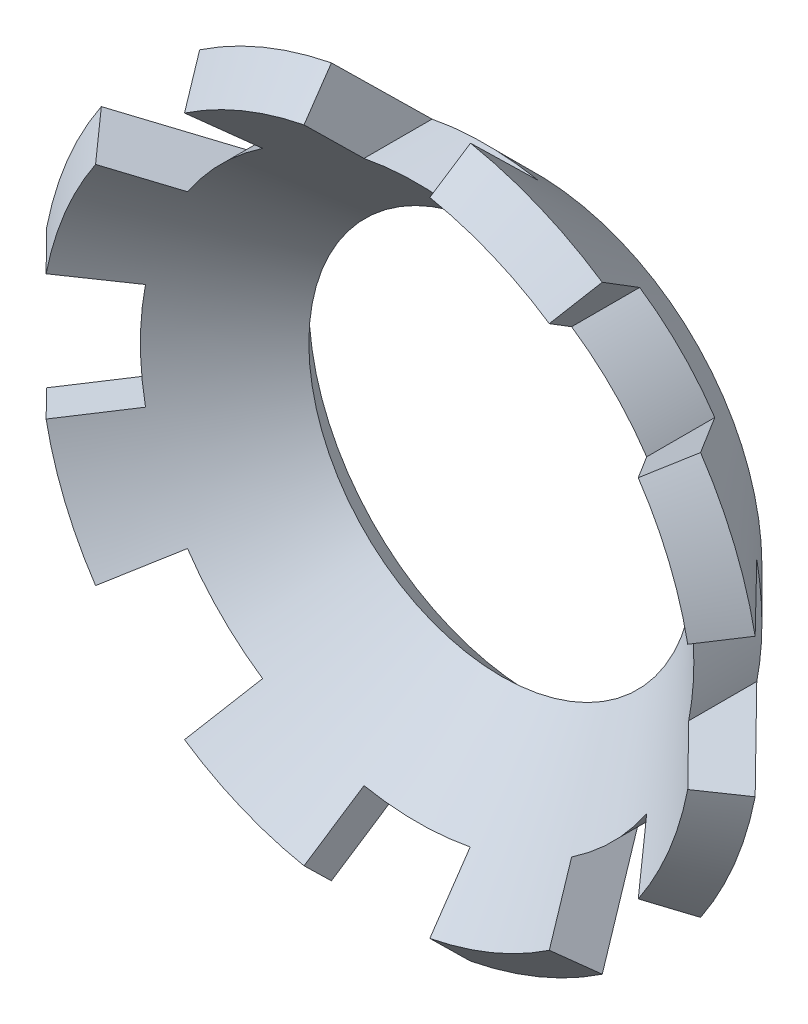
SolidWorks part; units mm, degrees
ref_plane "Front Plane" through (0, 0, 0) normal (0, 0, 1) x (1, 0, 0)
ref_plane "Top Plane" through (0, 0, 0) normal (0, 1, 0) x (1, 0, 0)
ref_plane "Right Plane" through (0, 0, 0) normal (1, 0, 0) x (0, 0, -1)
sketch "BodySke" plane through (0, 0, 0) normal (0, 1, 0) x (1, 0, 0)
  line L0 (0, -1.6) -> (0, 3.997) construction
  line L1 (0, 0) -> (3, 0) construction
  line L2 (3, 0) -> (0.5887, 2.4113) construction
  line L3 (3, 0) -> (1.8828, 1.1172)
  line L4 (3, 0) -> (2.7172, -0.2828)
  line L5 (2.7172, -0.2828) -> (1.6, 0.8343)
  line L6 (1.6, 0.8343) -> (1.8828, 1.1172)
  line L7 (0, 0) -> (-8, 0) construction
  dimension "Inner_dia" = 3.2
revolve "BaseBody" add sketch "BodySke" angle 360 about L0
sketch "ToothSke" plane through (0, 0, 0) normal (0, 0, 1) x (1, 0, 0)
  line L0 (0, 0) -> (4.8783, 0) construction
  line L1 (2.2573, 0.4413) -> (3, 0.589)
  line L2 (3, -0.589) -> (3, 0.589)
  line L3 (2.2573, -0.4413) -> (3, -0.589)
  circle A0 centre (0, 0) radius 3 construction
  circle A1 centre (0, 0) radius 3 construction
  arc A2 (-2.3, 0) -> (2.2573, 0.4413) centre (0, 0) ccw construction
  arc A3 (2.2573, -0.4413) -> (2.2573, 0.4413) centre (0, 0) ccw
  point P9 (3, 0)
  dimension "D1" = 4.6
  dimension "D2" = 1.1781
  dimension "D3" = 22.5
extrude "ToothCut" cut sketch "ToothSke" against normal through all and the other way through all
pattern_circular "ToothPat" count 8 over 360 about axis through (0, 0, 1.6) along (0, 0, -1) of "ToothCut"
equation "\"D1@ToothSke\" =  ( \"Outer_dia@BodySke\" + \"Inner_dia@BodySke\" )  / 2"
equation "\"D2@ToothSke\" = pi  * \"Outer_dia@BodySke\" / 2 / \"Num_tooth@BodySke\""
equation "\"Num_tooth@ToothPat\" = \"Num_tooth@BodySke\""
equation "\"D3@ToothSke\" = 360 / 2 / \"Num_tooth@BodySke\""
